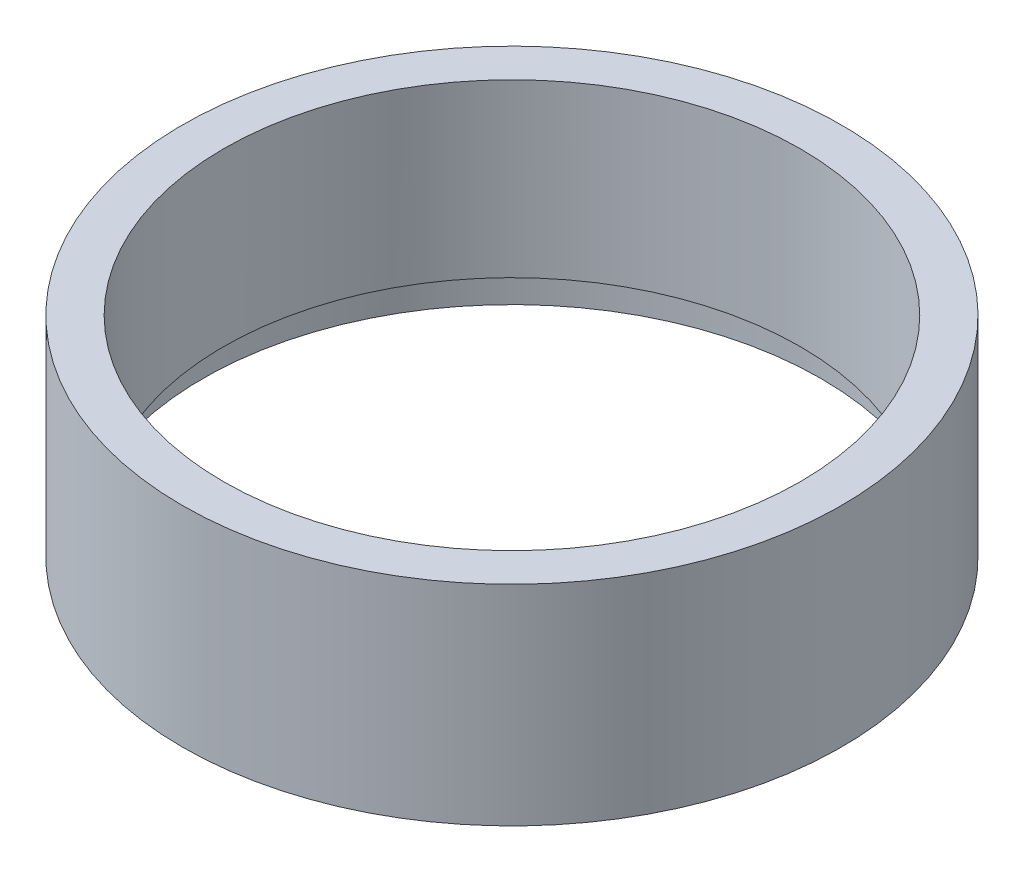
SolidWorks part; units mm, degrees
material "C (Graphite)"
ref_plane "Front Plane" through (0, 0, 0) normal (0, 0, 1) x (1, 0, 0)
ref_plane "Top Plane" through (0, 0, 0) normal (0, 1, 0) x (1, 0, 0)
ref_plane "Right Plane" through (0, 0, 0) normal (1, 0, 0) x (0, 0, -1)
sketch "Sketch1" plane through (0, 0, 0) normal (0, 1, 0) x (1, 0, 0)
  circle A0 centre (0, 0) radius 40
  circle A1 centre (0, 0) radius 35
  dimension "D1" = 80
  dimension "D2" = 70
extrude "Boss-Extrude1" add sketch "Sketch1" along normal blind 25.4
sketch "Sketch2" plane through (0, 0, 0) normal (0, -1, 0) x (1, 0, 0)
  circle A0 centre (0, 0) radius 37.5
  circle A1 centre (0, 0) radius 35
  dimension "D1" = 75
  dimension "D2" = 70
extrude "Cut-Extrude1" cut sketch "Sketch2" against normal blind 4.6
